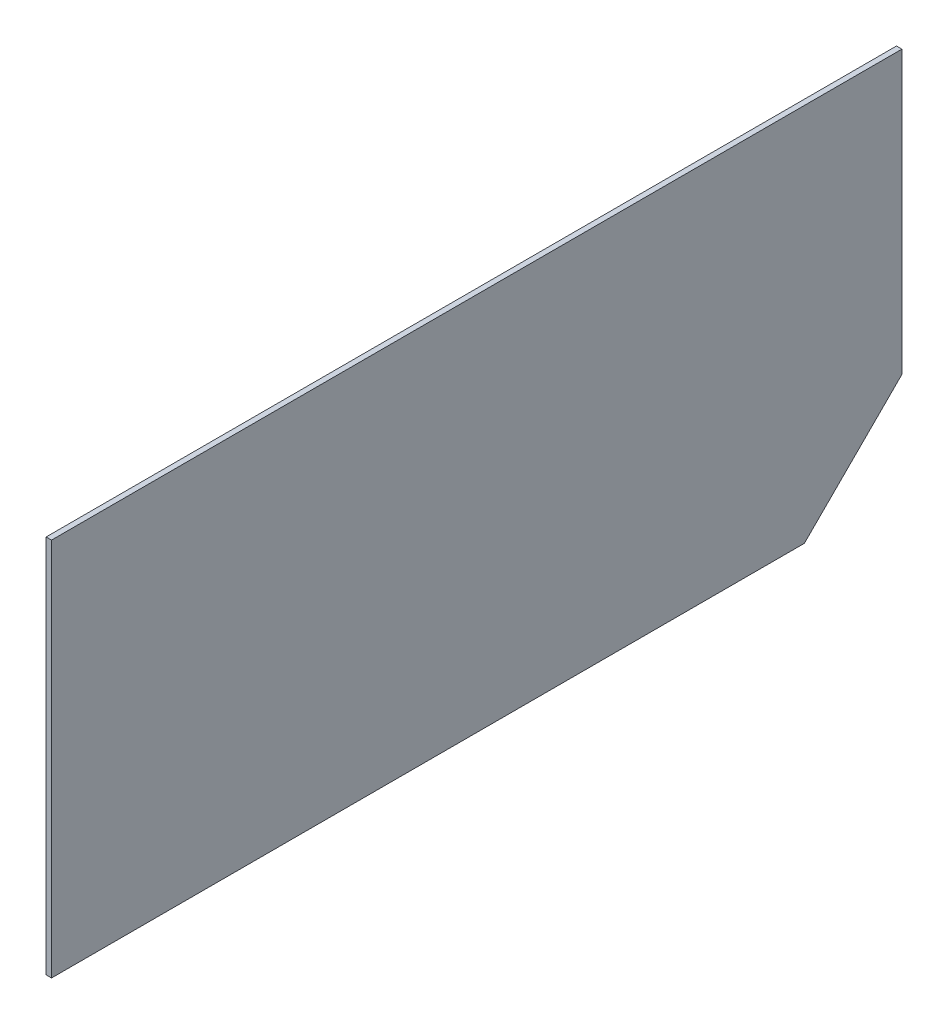
SolidWorks part; units mm, degrees
material "6061-T6 (SS)"
ref_plane "X-Y Datum" through (0, 0, 0) normal (0, 0, 1) x (1, 0, 0)
ref_plane "X-Z Datum" through (0, 0, 0) normal (0, 1, 0) x (1, 0, 0)
ref_plane "Y-Z Datum" through (0, 0, 0) normal (1, 0, 0) x (0, 0, -1)
sketch "Sketch1" plane through (0, 0, 0) normal (1, 0, 0) x (0, 0, -1)
  line L1 (-249.174, 82.55) -> (249.174, 82.55)
  line L2 (-249.174, 82.55) -> (-249.174, -82.55)
  line L3 (-249.174, -82.55) -> (249.174, -82.55)
  line L4 (249.174, 82.55) -> (249.174, -82.55)
  line L5 (-249.174, 82.55) -> (249.174, -82.55) construction
  line L6 (-249.174, -82.55) -> (249.174, 82.55) construction
  point P0 (0, 0)
  dimension "D1" = 165.1
  dimension "D2" = 498.348
extrude "Boss-Extrude1" add sketch "Sketch1" along normal mid plane 3.175
sketch "Sketch2" plane through (1.5875, 0, 0) normal (1, 0, 0) x (0, 0, -1)
  line L2 (249.174, -82.55) -> (192.024, -139.7)
  line L5 (-249.174, -82.55) -> (249.174, -82.55) construction
  line L6 (-249.174, -82.55) -> (249.174, -82.55)
  line L8 (192.024, -139.7) -> (-249.174, -139.7)
  line L9 (-249.174, -139.7) -> (-249.174, -82.55)
  line L11 (-249.174, 82.55) -> (-249.174, -82.55) construction
  line L12 (249.174, -82.55) -> (249.174, 82.55) construction
  point P1 (249.174, -89.8477)
  point P2 (189.6747, -136.525)
  point P5 (249.174, -88.9)
  line M10 (-249.174, -82.55) -> (249.174, -82.55)
  dimension "D1" = 45
  dimension "D5" = 57.15
extrude "Boss-Extrude2" add sketch "Sketch2" against normal blind 3.175 contours L2 M10 region at (1.5875, -110.5456, 13.9978)
